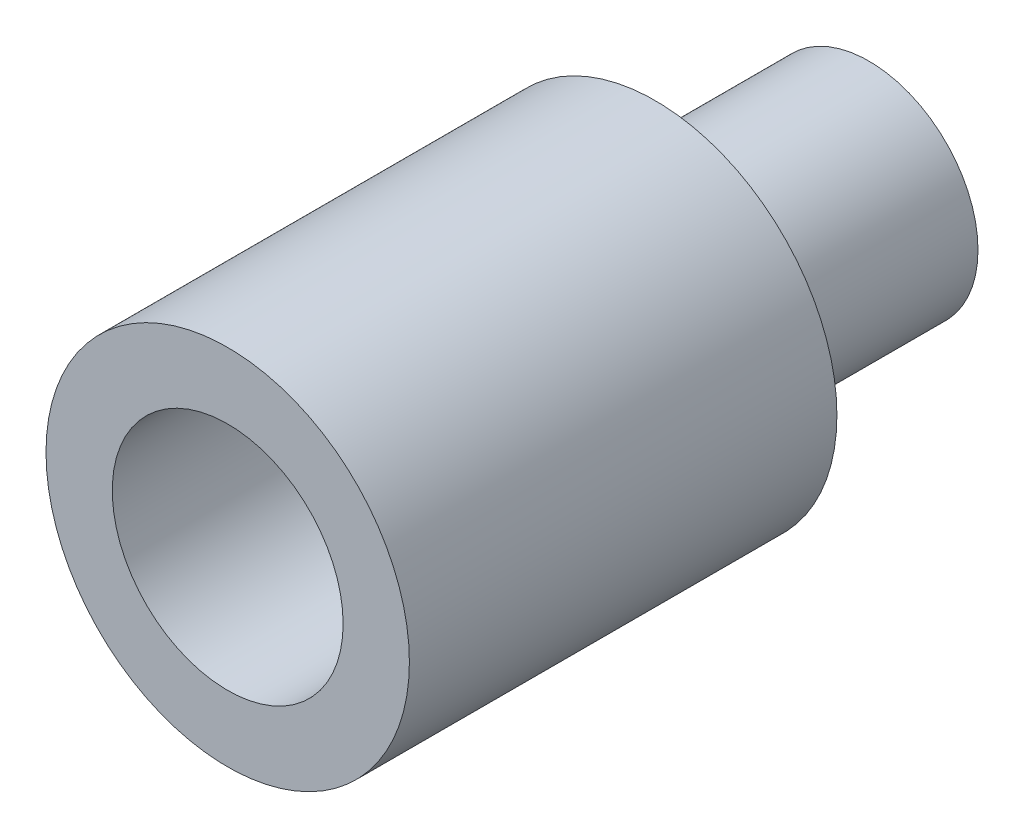
SolidWorks part; units mm, degrees
material "ABS"
ref_plane "X-Y Datum" through (0, 0, 0) normal (0, 0, 1) x (1, 0, 0)
ref_plane "X-Z Datum" through (0, 0, 0) normal (0, 1, 0) x (1, 0, 0)
ref_plane "Y-Z Datum" through (0, 0, 0) normal (1, 0, 0) x (0, 0, -1)
sketch "Sketch1" plane through (0, 0, 0) normal (0, 0, 1) x (1, 0, 0)
  circle A0 centre (0, 0) radius 2.55
  dimension "D1" = 5.1
extrude "Boss-Extrude1" add sketch "Sketch1" along normal blind 5
sketch "Sketch2" plane through (0, 0, 5) normal (0, 0, 1) x (1, 0, 0)
  circle A0 centre (0, 0) radius 4.25
  circle A1 centre (0, 0) radius 2.7 construction
  dimension "D1" = 5.4
  dimension "D2" = 8.5
extrude "Boss-Extrude2" add sketch "Sketch2" along normal blind 10 contours A0
sketch "Sketch3" plane through (0, 0, 15) normal (0, 0, 1) x (1, 0, 0)
  circle A0 centre (0, 0) radius 2.7
  dimension "D1" = 5.4
extrude "Cut-Extrude1" cut sketch "Sketch3" against normal blind 8
